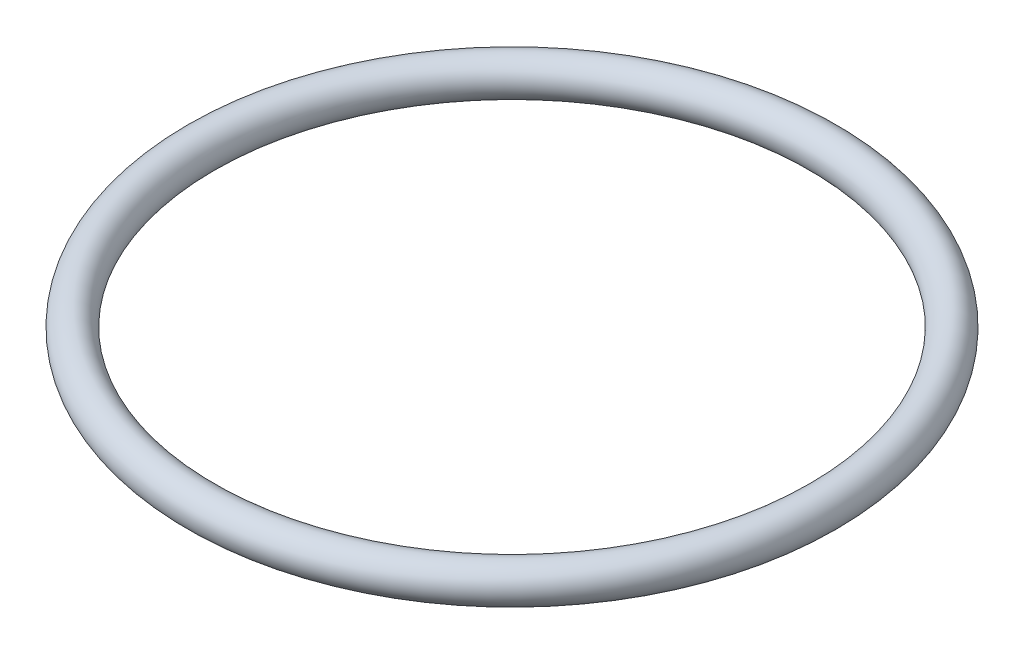
SolidWorks part; units mm, degrees
ref_plane "Plano frontal" through (0, 0, 0) normal (0, 0, 1) x (1, 0, 0)
ref_plane "Plano superior" through (0, 0, 0) normal (0, 1, 0) x (1, 0, 0)
ref_plane "Plano direito" through (0, 0, 0) normal (1, 0, 0) x (0, 0, -1)
sketch "Esboço1" plane through (0, 0, 0) normal (0, 1, 0) x (1, 0, 0)
  line L1 (0, 49.7625) -> (0, -49.7625) construction
  line L2 (-49.7625, 0) -> (49.7625, 0) construction
  circle A0 centre (0, 0) radius 45 construction
  circle A1 centre (0, 0) radius 49.7625 construction
  circle A2 centre (0, 0) radius 52.9375
  point P11 (0, 0)
  dimension "D1" = 90
  dimension "D2" = 4.7625
  dimension "D3" = 3.175
sketch "Esboço3" plane through (0, 0, 0) normal (0, 0, 1) x (1, 0, 0)
  circle A0 centre (-52.9375, 0) radius 3.175
  point P2 (0, 0)
  point P3 (0, 0)
  point P4 (-45, 0)
  point P5 (0, 0)
sweep "Varredura1" add profiles "Esboço3" path "Esboço1"
ref_axis "Eixo1" through (0, 0, 0) along (0, 1, 0)
ref_plane "Plano1" through (0, 0, 0) normal (0, 1, 0) x (1, 0, 0)
